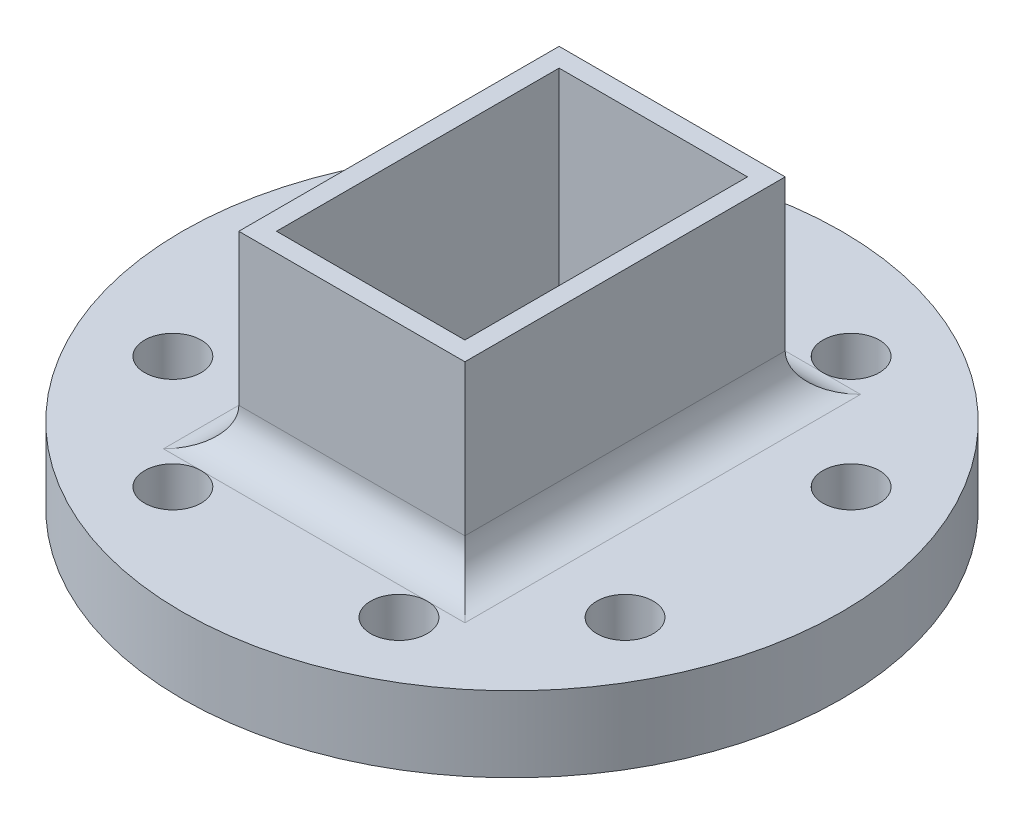
SolidWorks part; units mm, degrees
ref_plane "Front Plane" through (0, 0, 0) normal (0, 0, 1) x (1, 0, 0)
ref_plane "Top Plane" through (0, 0, 0) normal (0, 1, 0) x (1, 0, 0)
ref_plane "Right Plane" through (0, 0, 0) normal (1, 0, 0) x (0, 0, -1)
sketch "Sketch1" plane through (0, 0, 0) normal (0, 1, 0) x (1, 0, 0)
  line L0 (0, 0) -> (12, 6) construction
  line L1 (0, 0) -> (6, -12) construction
  circle A0 centre (0, 0) radius 13.4164
  circle A1 centre (12, 6) radius 1.5
  circle A2 centre (12, -6) radius 1.5
  circle A3 centre (-12, 6) radius 1.5
  circle A4 centre (-12, -6) radius 1.5
  circle A5 centre (6, 12) radius 1.5
  circle A6 centre (6, -12) radius 1.5
  circle A7 centre (-6, -12) radius 1.5
  circle A8 centre (-6, 12) radius 1.5
  circle A9 centre (0, 0) radius 17.5
  dimension "D1" = 3
  dimension "D6" = 35
  dimension "D2" = 12
  dimension "D3" = 24
  dimension "D5" = 90
  dimension "D4" = 2
extrude "Boss-Extrude1" add sketch "Sketch1" along normal blind 4 contours A8 A0 A3 A4 A7 A6 A2 A1 A5 | A9 A8 A0 A5 A1 A2 A6 A7 A4 A3 region at (0, 0, 0) region at (-17.005, 0, 0)
sketch "Sketch3" plane through (0, 4, 0) normal (0, 1, 0) x (1, 0, 0)
  line L0 (-6, 8.5) -> (6, 8.5)
  line L1 (-5, -7.5) -> (5, -7.5)
  line L2 (-5, -7.5) -> (-5, 7.5)
  line L3 (-5, 7.5) -> (5, 7.5)
  line L4 (5, -7.5) -> (5, 7.5)
  line L5 (-5, -7.5) -> (5, 7.5) construction
  line L6 (-5, 7.5) -> (5, -7.5) construction
  line L7 (6, -8.5) -> (6, 8.5)
  line L8 (-6, -8.5) -> (6, -8.5)
  line L9 (-6, -8.5) -> (-6, 8.5)
  point P0 (0, 0)
  dimension "D1" = 15
  dimension "D2" = 10
  dimension "D3" = 1
extrude "Boss-Extrude2" add sketch "Sketch3" along normal blind 10
fillet "Fillet1" radius 2 4 edges at (6, 4, 0) (0, 4, -8.5) (-6, 4, 0) (0, 4, 8.5)
